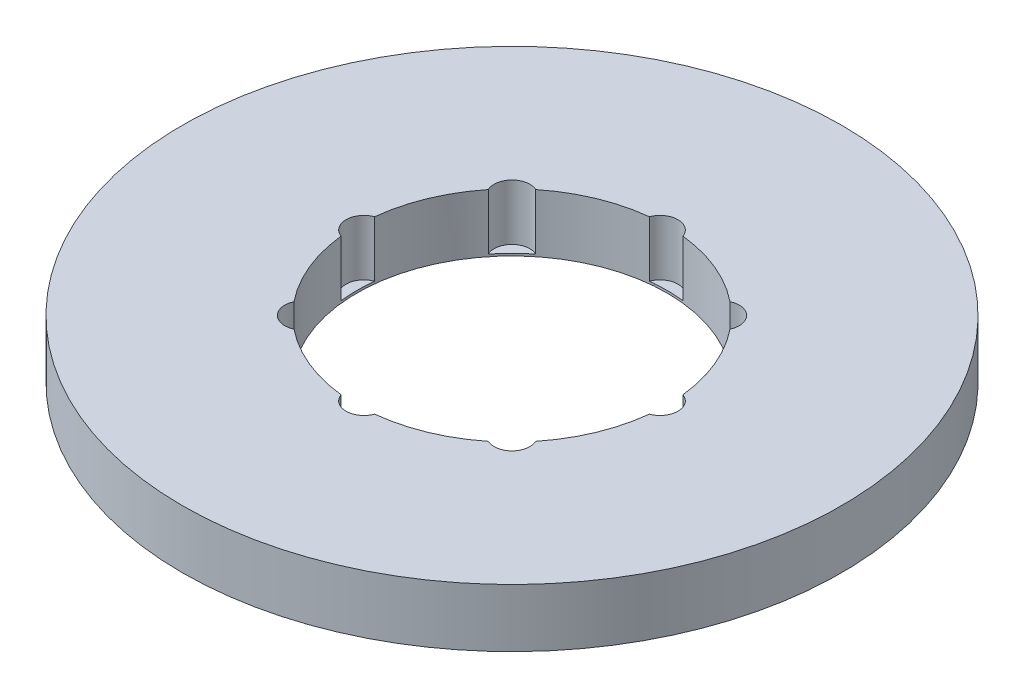
SolidWorks part; units mm, degrees
ref_plane "Front Plane" through (0, 0, 0) normal (0, 0, 1) x (1, 0, 0)
ref_plane "Top Plane" through (0, 0, 0) normal (0, 1, 0) x (1, 0, 0)
ref_plane "Right Plane" through (0, 0, 0) normal (1, 0, 0) x (0, 0, -1)
sketch "Sketch1" plane through (0, 0, 0) normal (0, 1, 0) x (1, 0, 0)
  circle A0 centre (0, 0) radius 85
  dimension "FLANGE_OD" = 170
extrude "Boss-Extrude1" add sketch "Sketch1" along normal blind 15
sketch "Sketch2" plane through (0, 0, 0) normal (0, 1, 0) x (1, 0, 0)
  circle A0 centre (0, 0) radius 40
  dimension "BORE_D" = 80
extrude "Cut-Extrude1" cut sketch "Sketch2" along normal through all
sketch "Sketch3" plane through (0, 15, 0) normal (0, 1, 0) x (1, 0, 0)
  circle A0 centre (0, 0) radius 38.1861 construction
  circle A1 centre (-38.1861, 0) radius 4.6086
  dimension "BOLT_D" = 9.2172
  dimension "BOLT_PCD" = 76.3723
extrude "Cut-Extrude2" cut sketch "Sketch3" against normal blind 14.4066
pattern_circular "CirPattern1" count 8 over 360 about axis through (0, 0, 0) along (0, 1, 0) of "Cut-Extrude2"
